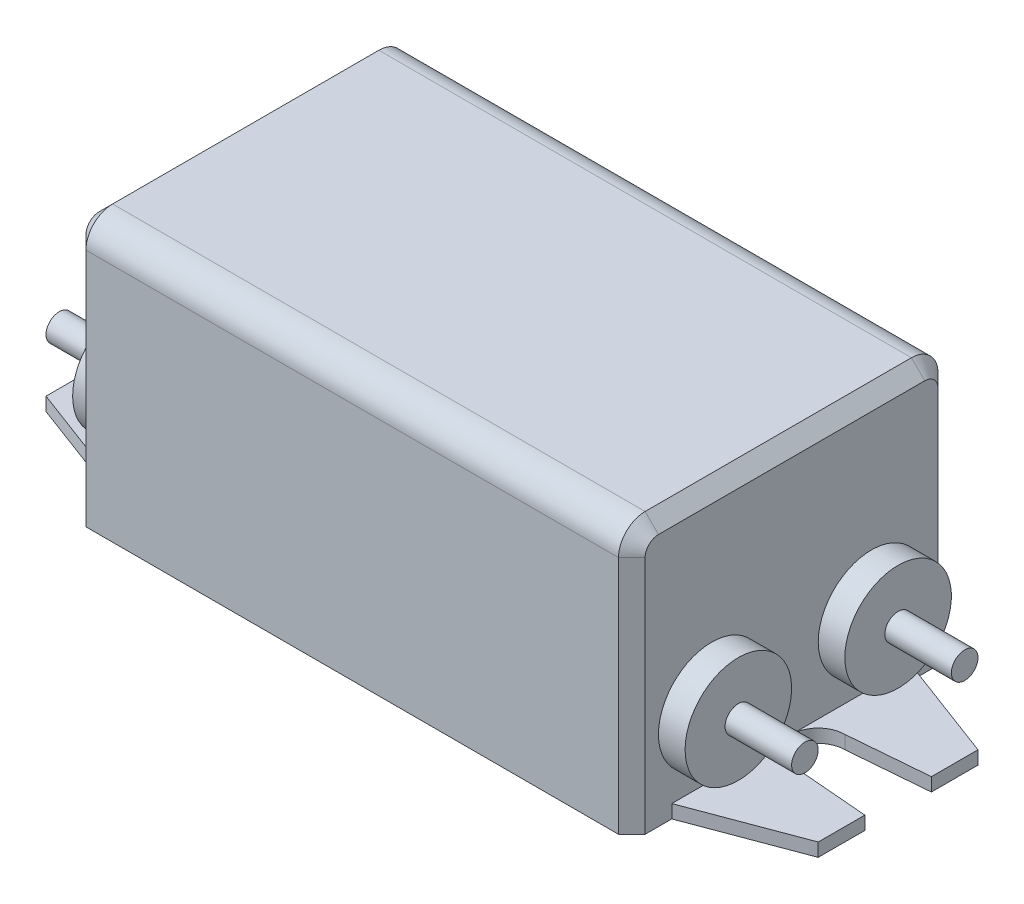
SolidWorks part; units mm, degrees
ref_plane "前视基准面" through (0, 0, 0) normal (0, 0, 1) x (1, 0, 0)
ref_plane "上视基准面" through (0, 0, 0) normal (0, 1, 0) x (1, 0, 0)
ref_plane "右视基准面" through (0, 0, 0) normal (1, 0, 0) x (0, 0, -1)
sketch "草图1" plane through (0, 0, 0) normal (0, 1, 0) x (1, 0, 0)
  line L0 (-20, 12) -> (20, 12)
  line L1 (-20, 12) -> (-20, -12)
  line L2 (20, 12) -> (20, -12)
  line L3 (-20, -12) -> (20, -12)
  line L4 (-20, 12) -> (20, -12) construction
  line L5 (20, 12) -> (-20, -12) construction
  line L6 (20, 12) -> (21, 12)
  line L7 (21, 12) -> (21, -12)
  line L8 (21, -12) -> (20, -12)
  line L9 (0, 12) -> (0, -12) construction
  line L10 (-21, -12) -> (-20, -12)
  line L11 (-21, 12) -> (-21, -12)
  line L12 (-20, 12) -> (-21, 12)
  line L13 (21, 0) -> (29, 0)
  line L14 (29, 6) -> (29, -6)
  line L15 (21, 9) -> (21, -9)
  line L16 (29, 6) -> (21, 9)
  line L17 (29, -6) -> (21, -9)
  line L18 (29, 2.5) -> (29, -2.5)
  line L21 (21, 0) -> (21, 2.5)
  line L22 (21, -2.5) -> (21, 0)
  line L23 (21, 0) -> (23, 0)
  line L24 (29, 2.5) -> (23, 2)
  line L25 (29, -2.5) -> (23, -2)
  line L26 (-29, -2.5) -> (-23, -2)
  line L27 (-29, 2.5) -> (-23, 2)
  line L28 (-21, 0) -> (-23, 0)
  line L29 (-29, 2.5) -> (-29, -2.5)
  line L30 (-29, -6) -> (-21, -9)
  line L31 (-29, 6) -> (-21, 9)
  line L32 (-29, 6) -> (-29, -6)
  line L33 (-21, 0) -> (-29, 0)
  arc A0 (23, 2) -> (23, -2) centre (23, 0) ccw
  arc A1 (-23, 2) -> (-23, -2) centre (-23, 0) cw
  point P1 (0, 0)
  point P17 (29, 0)
  point P20 (21, 0)
  point P23 (29, 0)
  point P39 (-29, 0)
  point P40 (-29, 0)
  dimension "D1" = 40
  dimension "D2" = 24
  dimension "D3" = 1
  dimension "D4" = 8
  dimension "D5" = 6
  dimension "D6" = 9
  dimension "D7" = 2.5
  dimension "D8" = 2
extrude "凸台-拉伸1" add sketch "草图1" along normal blind 20 contours L1 L3 L2 L0 region at (0, 0, 0)
extrude "凸台-拉伸2" add sketch "草图1<4>" along normal blind 1 separate body contours L27 A1 L11 L31 L32 | L11 A1 L26 L32 L30 | A0 L24 L14 L16 L7 L15 | A0 L7 L15 L17 L14 L25 region at (-24.4914, 0, -4.8453) region at (24.4914, 0, -4.8453) region at (-24.4914, 0, 4.8453) region at (24.4914, 0, 4.8453)
sketch "草图1<4>" plane through (0, 0, 0) normal (0, 1, 0) x (1, 0, 0) same geometry as "草图1"
extrude "凸台-拉伸4" add sketch "草图1<6>" along normal blind 20 contours L1 L12 L11 L10 | L8 L7 L15 L6 L2 region at (-20.5, 0, 0) region at (20.5, 0, 0)
sketch "草图1<6>" plane through (0, 0, 0) normal (0, 1, 0) x (1, 0, 0) same geometry as "草图1"
sketch "草图2" plane through (-21, 0, 0) normal (-1, 0, 0) x (0, 0, 1)
  line L0 (0, 0) -> (0, 6)
  line L1 (12, 6) -> (10, 6)
  line L2 (12, 20) -> (12, 0) construction
  line L3 (10, 6) -> (6, 6)
  circle A0 centre (6, 6) radius 4
  circle A1 centre (-6, 6) radius 4
  dimension "D1" = 6
  dimension "D2" = 2
  dimension "D3" = 4
extrude "凸台-拉伸5" add sketch "草图2" along normal blind 2 contours A1 | A0 region at (-21, 6, -6)
mirror "镜向1" about plane through (0, 0, 0) normal (1, 0, 0) of "凸台-拉伸5"
fillet "圆角1" radius 2 2 edges at (0, 20, -12) (0, 20, 12)
chamfer "倒角1" distance 1 angle 45 5 edges at (21, 9, -12) (21, 9, 12) (21, 19.4142, -11.4142) (21, 19.4142, 11.4142) (21, 20, 0)
chamfer "倒角2" distance 1 angle 45 5 edges at (-21, 9, -12) (-21, 9, 12) (-21, 19.4142, -11.4142) (-21, 19.4142, 11.4142) (-21, 20, 0)
sketch "草图3" plane through (-23, 0, 0) normal (-1, 0, 0) x (0, 0, 1)
  circle A0 centre (6, 6) radius 1
  dimension "D1" = 2
extrude "凸台-拉伸6" add sketch "草图3" along normal blind 5
mirror "镜向2" about plane through (0, 0, 0) normal (0, 0, 1) of "凸台-拉伸6"
mirror "镜向3" about plane through (0, 0, 0) normal (1, 0, 0) of "凸台-拉伸6"
mirror "镜向4" about plane through (0, 0, 0) normal (1, 0, 0) of "镜向2"
